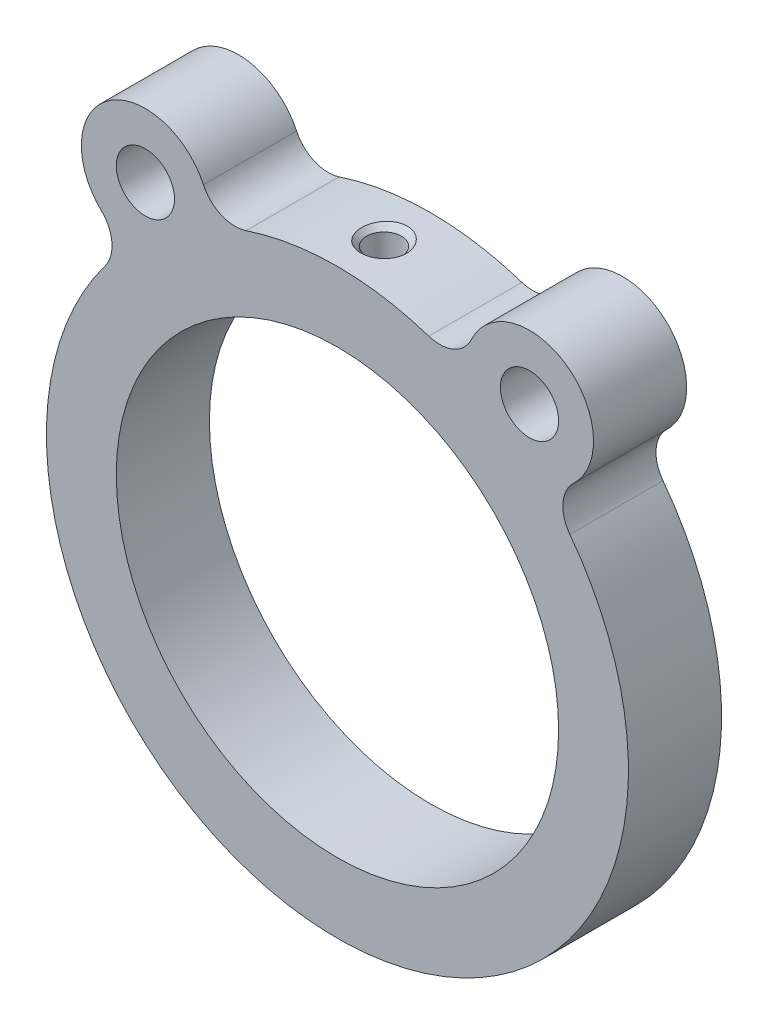
SolidWorks part; units mm, degrees
material "Brass"
ref_plane "Front Plane" through (0, 0, 0) normal (0, 0, 1) x (1, 0, 0)
ref_plane "Top Plane" through (0, 0, 0) normal (0, 1, 0) x (1, 0, 0)
ref_plane "Right Plane" through (0, 0, 0) normal (1, 0, 0) x (0, 0, -1)
sketch "Sketch1" plane through (0, 0, 0) normal (0, 0, 1) x (1, 0, 0)
  line L0 (0, 0) -> (0, 23)
  line L1 (0, 23) -> (16.5, 23)
  line L2 (0, 23) -> (-16.5, 23)
  circle A0 centre (0, 0) radius 19
  circle A1 centre (0, 0) radius 25
  circle A2 centre (16.5, 23) radius 2.5
  circle A3 centre (-16.5, 23) radius 2.5
  circle A4 centre (16.5, 23) radius 5.5
  circle A5 centre (-16.5, 23) radius 5.5
  circle A6 centre (-22.3645, 16.8472) radius 3
  circle A7 centre (-8.7924, 26.5837) radius 3
  circle A8 centre (8.7924, 26.5837) radius 3
  circle A9 centre (22.3645, 16.8472) radius 3
  dimension "D1" = 23
  dimension "D4" = 5
  dimension "D5" = 5
  dimension "D6" = 11
  dimension "D7" = 11
  dimension "D8" = 50
  dimension "D9" = 38
  dimension "D2" = 16.5
  dimension "D3" = 16.5
extrude "Boss-Extrude1" add sketch "Sketch1" along normal blind 4 and the other way blind 4 contours A5 A1 A4 L1 A0 L2 | A1 A4 | A4 L1 A1 | A8 A1 L1 A4 | A5 A1 L2 | A7 A5 L2 A1 | A6 A1 A5 | A9 A4 A1 | A4 A1 A2 | L1 A1 L2 | A5 A1 A3 | A1 A5 region at (4.899, 22.3069, 0) region at (0, 23.8028, 0) region at (10.2341, 23.599, 0) region at (10.6105, 22.815, 0) region at (-10.6105, 22.815, 0) region at (-10.2341, 23.599, 0) region at (11.2807, 24.1541, 0) region at (14.0131, 19.5334, 0) region at (-11.1617, 22.7254, 0) region at (-14.0131, 19.5334, 0) region at (18.9519, 17.2715, 0) region at (-18.9519, 17.2715, 0)
sketch "Sketch2" plane through (0, 0, 0) normal (0, 1, 0) x (1, 0, 0)
  circle A0 centre (0, 0) radius 1.5
sketch "Sketch3" plane through (0, 0, 0) normal (0, 0, 1) x (1, 0, 0)
  line L0 (0, 25) -> (5.6581, 25)
  arc A0 (7.8504, 23.7355) -> (-7.8504, 23.7355) centre (0, 0) ccw construction
ref_plane "Plane1" through (0, 25, 0) normal (0, -1, 0) x (1, 0, 0)
sketch "Sketch4" plane through (0, 25, 0) normal (0, -1, 0) x (1, 0, 0)
  circle A0 centre (0, 0) radius 1.5
  point P0 (0, 0)
hole_wizard "CSK for ST2.2 Cross recessed CTSK head tapping screws1" positions "Sketch4" profile "Sketch7" countersink size "ST2.2" standard "GB"
sketch "Sketch7" plane through (0, 25, 0) normal (1, 0, 0) x (0, 0, 1)
  line L0 (0, 0) -> (0, 11.0013)
  line L1 (0, 11.0013) -> (1.5, 10.1)
  line L2 (1.5, 10.1) -> (1.5, 0.5)
  line L3 (1.5, 0.5) -> (2, 0)
  line L5 (2, 0) -> (0, 0)
  line L6 (-1.5, 0.5) -> (-2, 0) construction
  line L10 (0, 11.0013) -> (-1.5, 10.1) construction
  line L11 (0, -6.35) -> (0, 107.95) construction
  dimension "Hole Dia." = 3
  dimension "Hole Depth" = 10.1
  dimension "Near C'Sink Dia." = 4
  dimension "Near C'Sink Angle" = 90
  dimension "Drill Angle" = 118
